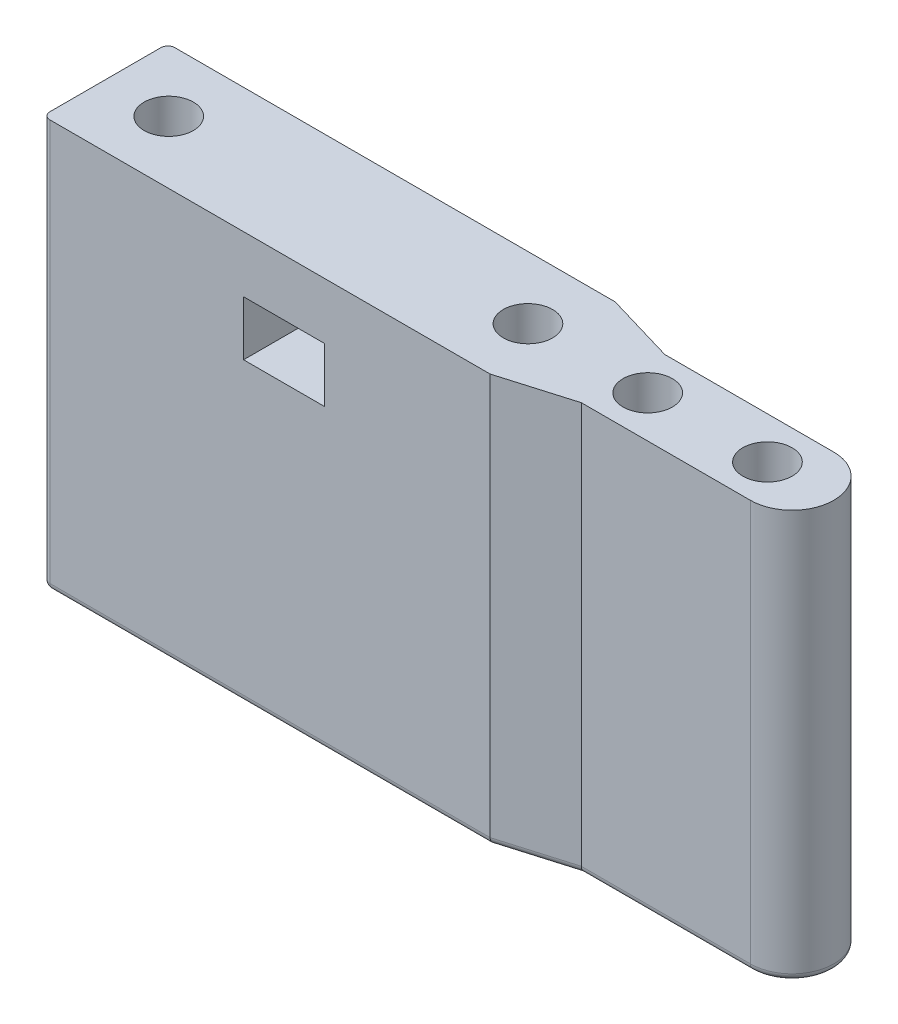
SolidWorks part; units mm, degrees
ref_plane "Front Plane" through (0, 0, 0) normal (0, 0, 1) x (1, 0, 0)
ref_plane "Top Plane" through (0, 0, 0) normal (0, 1, 0) x (1, 0, 0)
ref_plane "Right Plane" through (0, 0, 0) normal (1, 0, 0) x (0, 0, -1)
sketch "Sketch1" plane through (0, 0, 0) normal (0, 0, 1) x (1, 0, 0)
  line L1 (-58.9649, 34.1548) -> (-47.4649, 34.1548)
  line L2 (-58.9649, 34.1548) -> (-58.9649, 26.4048)
  line L3 (-58.9649, 26.4048) -> (-47.4649, 26.4048)
  line L4 (-47.4649, 34.1548) -> (-47.4649, 26.4048)
  line L5 (-87.4649, 42.1548) -> (16.5351, 42.1548)
  line L6 (-87.4649, 42.1548) -> (-87.4649, -15.8452)
  line L7 (-87.4649, -15.8452) -> (16.5351, -15.8452)
  line L8 (16.5351, 42.1548) -> (16.5351, -15.8452)
  dimension "D1" = 11.5
  dimension "D2" = 7.75
  dimension "D3" = 104
  dimension "D4" = 50
  dimension "D5" = 8
  dimension "D6" = 28.5
  dimension "D7" = 58
extrude "modular_main_body" add sketch "Sketch1" along normal blind 17.75
sketch "Sketch2" plane through (0, -15.8452, 0) normal (0, -1, 0) x (1, 0, 0)
  line L0 (16.5351, 17.75) -> (16.5351, 0) construction
  line L1 (-87.4649, 17.75) -> (16.5351, 17.75) construction
  line L2 (-87.4649, 17.75) -> (-87.4649, 0) construction
  line L3 (-23.9649, 17.75) -> (-13.9649, 14.8)
  line L8 (-87.4649, 0) -> (16.5351, 0) construction
  line L9 (10.0351, 17.75) -> (10.0351, 0) construction
  line L11 (-13.9649, 14.8) -> (10.0351, 14.8)
  line L12 (10.0351, 2.95) -> (-13.9649, 2.95)
  line L14 (-23.9649, 0) -> (-13.9649, 2.95)
  line L15 (-23.9649, 17.75) -> (16.5351, 17.75)
  line L16 (16.5351, 17.75) -> (16.5351, 0)
  line L17 (16.5351, 0) -> (-23.9649, 0)
  arc A0 (10.0351, 2.95) -> (10.0351, 14.8) centre (10.0351, 8.875) ccw
  dimension "D1" = 11.85
  dimension "D2" = 6.5
  dimension "D3" = 0
  dimension "D4" = 24
  dimension "D5" = 24
  dimension "D6" = 0
  dimension "D7" = 63.5
  dimension "D8" = 0
  dimension "D9" = 63.5
extrude "front_cut_out" cut sketch "Sketch2" against normal through all
sketch "Sketch5" plane through (0, 42.1548, 0) normal (0, 1, 0) x (1, 0, 0)
  line L1 (-87.4649, -17.75) -> (-87.4649, 0) construction
  line L2 (-78.4649, 0) -> (-78.4649, -17.75) construction
  line L3 (-23.9649, 0) -> (-87.4649, 0) construction
  line L4 (-23.9649, -17.75) -> (-87.4649, -17.75) construction
  circle A0 centre (-78.4649, -8.875) radius 3.5
  circle A3 centre (-27.4649, -8.875) radius 3.5
  circle A4 centre (-10.4649, -8.875) radius 3.5
  circle A5 centre (6.5351, -8.875) radius 3.5
  circle A6 centre (-61.4649, -8.875) radius 3.5 [skipped]
  circle A7 centre (-44.4649, -8.875) radius 3.5 [skipped]
  dimension "D1" = 7
  dimension "D3" = 9
  dimension "D5" = 51
  dimension "D4" = 6
extrude "modular_interface_deep_cut_out" cut sketch "Sketch5" against normal blind 10
fillet "Fillet1" radius 1 8 edges at (-87.4649, -15.8452, 8.875) (-55.7149, -15.8452, 17.75) (-18.9649, -15.8452, 16.275) (-1.9649, -15.8452, 14.8) (15.9601, -15.8452, 8.875) (-1.9649, -15.8452, 2.95) (-18.9649, -15.8452, 1.475) (-55.7149, -15.8452, 0)
fillet "Fillet3" radius 1 4 edges at (-87.172, -15.5523, 17.4571) (-87.172, -15.5523, 0.2929) (-87.4649, 13.6548, 17.75) (-87.4649, 13.6548, 0)
